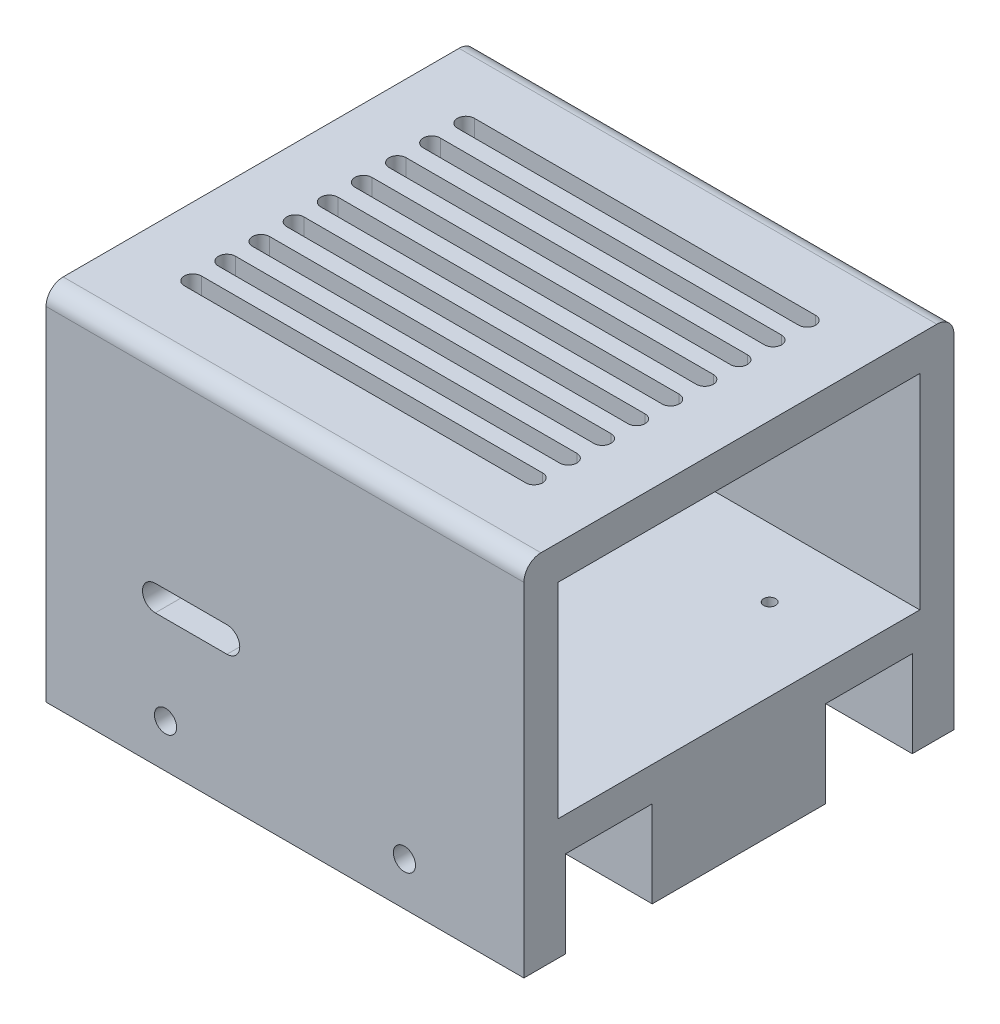
SolidWorks part; units mm, degrees
material "PETG"
ref_plane "Front Plane" through (0, 0, 0) normal (0, 0, 1) x (1, 0, 0)
ref_plane "Top Plane" through (0, 0, 0) normal (0, 1, 0) x (1, 0, 0)
ref_plane "Right Plane" through (0, 0, 0) normal (1, 0, 0) x (0, 0, -1)
sketch "Sketch1" plane through (0, 0, 0) normal (0, 1, 0) x (1, 0, 0)
  line L0 (-57.3, 38.1) -> (-70, 38.1) construction
  line L1 (-70, -25.395) -> (70, -25.395)
  line L2 (-70, -25.395) -> (-70, 25.395)
  line L3 (-70, 25.395) -> (70, 25.395)
  line L4 (70, -25.395) -> (70, 25.395)
  line L5 (-70, 52.5) -> (70, 52.5)
  line L6 (-70, 52.5) -> (-70, -52.5)
  line L7 (-70, -52.5) -> (70, -52.5)
  line L8 (70, 52.5) -> (70, -52.5)
  line L11 (57.3, 38.1) -> (70, 38.1) construction
  circle A0 centre (-57.3, 38.1) radius 3.25
  circle A1 centre (57.3, 38.1) radius 3.25
  circle A2 centre (-57.3, -38.1) radius 3.25
  circle A3 centre (57.3, -38.1) radius 3.25
  point P4 (-70, 0)
  point P5 (0, 25.395)
  dimension "D4" = 6.5
  dimension "D1" = 50.79
  dimension "D2" = 140
  dimension "D3" = 105
  dimension "D5" = 38.1
  dimension "D6" = 12.7
  dimension "D7" = 38.1
extrude "Boss-Extrude1" add sketch "Sketch1" along normal blind 10 contours L1 L4 L3 L2 | L8 L1 L6 L7 | L8 L5 L6 L3 | A1 | A0 | A2 | A3 region at (0, 0, 0) region at (0, 0, 38.9626) region at (0, 0, -38.9626) region at (-57.3, 0, -38.1) region at (57.3, 0, -38.1) region at (-57.3, 0, 38.1) region at (57.3, 0, 38.1)
extrude "Boss-Extrude2" add sketch "Sketch1<3>" against normal blind 25.4 contours L1 L4 L3 L2 region at (0, 0, 0)
sketch "Sketch1<3>" plane through (0, 0, 0) normal (0, 1, 0) x (1, 0, 0) same geometry as "Sketch1"
sketch "Sketch2" plane through (0, 10, 0) normal (0, 1, 0) x (1, 0, 0)
  line L0 (-46, 33) -> (-46, -46) construction
  line L1 (-46, -46) -> (46, -46) construction
  line L2 (46, -46) -> (46, 33) construction
  line L3 (46, 33) -> (-46, 33) construction
  line L4 (-70, -52.5) -> (70, -52.5) construction
  line L6 (-70, 52.5) -> (70, 52.5) construction
  line L7 (46, 0) -> (-46, 0) construction
  circle A0 centre (-46, 33) radius 4.5
  circle A1 centre (-46, 33) radius 1.75
  circle A2 centre (46, 33) radius 4.5
  circle A3 centre (46, 33) radius 1.75
  circle A4 centre (46, -46) radius 4.5
  circle A5 centre (46, -46) radius 1.75
  circle A6 centre (-46, -46) radius 4.5
  circle A7 centre (-46, -46) radius 1.75
  point P19 (0, 0)
  dimension "D1" = 3.5
  dimension "D2" = 9
  dimension "D3" = 6.5
  dimension "D4" = 92
  dimension "D5" = 19.5
extrude "Cut-Extrude4" cut sketch "Sketch2" against normal up to next contours A1 | A3 | A5 | A7 region at (-46, 10, -33)
sketch "Sketch3" plane through (0, 0, 0) normal (0, 1, 0) x (1, 0, 0)
  circle A0 centre (-46, 33) radius 3.2
  circle A1 centre (46, 33) radius 3.2
  circle A2 centre (46, -46) radius 3.2
  circle A3 centre (-46, -46) radius 3.2
  dimension "D1" = 6.4
extrude "Cut-Extrude3" cut sketch "Sketch3" along normal offset from surface (6.5 mm away) 3.5 up to face at (-46, 10, 47.75)
sketch "Sketch5" plane through (-70, 0, 0) normal (-1, 0, 0) x (0, 0, 1)
  line L0 (52.5, 10) -> (-52.5, 10) construction
  line L1 (-53, 0) -> (-63, 0)
  line L2 (-53, 0) -> (-53, 80)
  line L3 (-53, 80) -> (-63, 80)
  line L4 (-63, 0) -> (-63, 80)
  line L6 (-52.5, 10) -> (-53, 10)
  line L7 (53, 0) -> (63, 0)
  line L8 (53, 0) -> (53, 80)
  line L9 (53, 80) -> (63, 80)
  line L10 (63, 0) -> (63, 80)
  line L11 (-52.5, 10) -> (-52.5, 0)
  line L12 (-52.5, 0) -> (-53, 0)
  line L13 (-53, 80) -> (53, 80)
  line L14 (-53, 80) -> (-53, 70)
  line L15 (-53, 70) -> (53, 70)
  line L16 (53, 80) -> (53, 70)
  line L17 (-53, 10) -> (-53, 0)
  line L18 (52.5, 10) -> (53, 10)
  line L19 (52.5, 10) -> (52.5, 0)
  line L20 (52.5, 0) -> (53, 0)
  line L21 (53, 10) -> (53, 0)
  line M9 (52.5, 0) -> (52.5, 10)
  line M11 (-52.5, 10) -> (-52.5, 0)
  dimension "D1" = 10
  dimension "D2" = 60
  dimension "D3" = 0.5
extrude "Boss-Extrude3" add sketch "Sketch5" against normal up to surface (140 mm away) contours L4 L1 L2 L3 | L12 L6 L2 M11 | L2 L15 L8 L13 | L7 L10 L9 L8 | L20 L8 L18 M9 region at (-70, 40, -58) region at (-70, 5, -52.75) region at (-70, 75, 0) region at (-70, 40, 58) region at (-70, 5, 52.75) up to face at (70, -3.85, 0)
sketch "Sketch6" plane through (0, 0, 63) normal (0, 0, 1) x (1, 0, 0)
  line L0 (-38, 17) -> (-17, 17) construction
  line L1 (-38, 20.75) -> (-17, 20.75)
  line L2 (-38, 13.25) -> (-17, 13.25)
  line L3 (-70, 0) -> (-70, 80) construction
  line L4 (70, 0) -> (-70, 0) construction
  arc A0 (-38, 20.75) -> (-38, 13.25) centre (-38, 17) ccw
  arc A1 (-17, 13.25) -> (-17, 20.75) centre (-17, 17) ccw
  point P2 (-27.5, 17)
  dimension "D1" = 32
  dimension "D2" = 21
  dimension "D3" = 7.5
  dimension "17" = 17
extrude "Cut-Extrude6" cut sketch "Sketch6" against normal up to next
sketch "Sketch7" plane through (-70, 0, 0) normal (-1, 0, 0) x (0, 0, 1)
  line L0 (-25.395, 0) -> (-63, 0) construction
  line L1 (-63, 0) -> (-50.805, 0)
  line L2 (-63, 0) -> (-63, -25.4)
  line L3 (-63, -25.4) -> (-50.805, -25.4)
  line L4 (-50.805, 0) -> (-50.805, -25.4)
  line L5 (25.395, -25.4) -> (-25.395, -25.4) construction
  line L6 (-25.395, -25.4) -> (-25.395, 0) construction
  line L8 (63, 0) -> (50.805, 0)
  line L9 (63, 0) -> (63, -25.4)
  line L10 (63, -25.4) -> (50.805, -25.4)
  line L11 (50.805, 0) -> (50.805, -25.4)
  dimension "D1" = 25.41
extrude "Boss-Extrude4" add sketch "Sketch7" against normal up to surface (140 mm away) up to face at (70, 13.65, 0)
sketch "Sketch8" plane through (0, 0, -63) normal (0, 0, -1) x (-1, 0, 0)
  line L0 (-70, -25.4) -> (70, -25.4) construction
  line L1 (-70, 80) -> (-70, -25.4) construction
  line L2 (0, 0) -> (0, 50000) construction
  circle A0 centre (-35, -12.7) radius 3.25
  circle A2 centre (35, -12.7) radius 3.25
  dimension "D1" = 6.5
  dimension "D2" = 12.7
  dimension "D3" = 35
extrude "Cut-Extrude7" cut sketch "Sketch8" against normal up to next
mirror "Mirror1" about plane through (0, 0, 0) normal (0, 0, 1) of "Cut-Extrude7"
fillet "Fillet1" radius 5 2 edges at (0, 80, 63) (0, 80, -63)
sketch "Sketch9" plane through (0, 80, 0) normal (0, 1, 0) x (1, 0, 0)
  line L0 (-50, 40) -> (50, 40) construction
  line L1 (-50, 42.5) -> (50, 42.5)
  line L2 (-50, 37.5) -> (50, 37.5)
  line L3 (-50, 30) -> (50, 30) construction
  line L4 (-50, 32.5) -> (50, 32.5)
  line L5 (-50, 27.5) -> (50, 27.5)
  line L6 (-50, 20) -> (50, 20) construction
  line L7 (-50, 22.5) -> (50, 22.5)
  line L8 (-50, 17.5) -> (50, 17.5)
  line L9 (-50, 10) -> (50, 10) construction
  line L10 (-50, 12.5) -> (50, 12.5)
  line L11 (-50, 7.5) -> (50, 7.5)
  line L12 (-50, 0) -> (50, 0) construction
  line L13 (-50, 2.5) -> (50, 2.5)
  line L14 (-50, -2.5) -> (50, -2.5)
  line L15 (-50, -10) -> (50, -10) construction
  line L16 (-50, -7.5) -> (50, -7.5)
  line L17 (-50, -12.5) -> (50, -12.5)
  line L18 (-50, -20) -> (50, -20) construction
  line L19 (-50, -17.5) -> (50, -17.5)
  line L20 (-50, -22.5) -> (50, -22.5)
  line L21 (-50, 40) -> (-50, 30) construction
  line L22 (-50, -30) -> (50, -30) construction
  line L23 (-50, -27.5) -> (50, -27.5)
  line L24 (-50, -32.5) -> (50, -32.5)
  line L25 (-50, -40) -> (50, -40) construction
  line L26 (-50, -37.5) -> (50, -37.5)
  line L27 (-50, -42.5) -> (50, -42.5)
  arc A0 (-50, 42.5) -> (-50, 37.5) centre (-50, 40) ccw
  arc A1 (50, 37.5) -> (50, 42.5) centre (50, 40) ccw
  arc A2 (-50, 32.5) -> (-50, 27.5) centre (-50, 30) ccw
  arc A3 (50, 27.5) -> (50, 32.5) centre (50, 30) ccw
  arc A4 (-50, 22.5) -> (-50, 17.5) centre (-50, 20) ccw
  arc A5 (50, 17.5) -> (50, 22.5) centre (50, 20) ccw
  arc A6 (-50, 12.5) -> (-50, 7.5) centre (-50, 10) ccw
  arc A7 (50, 7.5) -> (50, 12.5) centre (50, 10) ccw
  arc A8 (-50, 2.5) -> (-50, -2.5) centre (-50, 0) ccw
  arc A9 (50, -2.5) -> (50, 2.5) centre (50, 0) ccw
  arc A10 (-50, -7.5) -> (-50, -12.5) centre (-50, -10) ccw
  arc A11 (50, -12.5) -> (50, -7.5) centre (50, -10) ccw
  arc A12 (-50, -17.5) -> (-50, -22.5) centre (-50, -20) ccw
  arc A13 (50, -22.5) -> (50, -17.5) centre (50, -20) ccw
  arc A14 (-50, -27.5) -> (-50, -32.5) centre (-50, -30) ccw
  arc A15 (50, -32.5) -> (50, -27.5) centre (50, -30) ccw
  arc A16 (-50, -37.5) -> (-50, -42.5) centre (-50, -40) ccw
  arc A17 (50, -42.5) -> (50, -37.5) centre (50, -40) ccw
  point P2 (0, 40)
  point P10 (0, 30)
  point P19 (0, 20)
  point P26 (0, 10)
  point P33 (0, 0)
  point P40 (0, -10)
  point P47 (0, -20)
  point P54 (0, -30)
  point P61 (0, -40)
  dimension "D1" = 100
  dimension "D2" = 5
  dimension "D3" = 40
  dimension "D5" = 10
  dimension "D4" = 9
extrude "Cut-Extrude8" cut sketch "Sketch9" against normal up to next
equation "\"tol_dia_id_intfc\" = 0.0200mm ' For hole diameters - Interference fit"
equation "\"tol_dia_id_slip\"  = 0.0300mm ' For hole diameters - Slip fit"
equation "\"tol_dia_id_clear\" = 0.0500mm ' For hole diameters - Clearance fit"
equation "\"tol_dia_od_intfc\" = 0.0200mm ' For shaft diameters - Interference fit"
equation "\"tol_dia_od_slip\"  = 0.0300mm ' For shaft diameters - Slip fit"
equation "\"tol_dia_od_clear\" = 0.0500mm ' For shaft diameters - Clearance fit"
equation "\"tol_general_intfc\"= 0.0030mm ' For general parts (Horiz) - Interference fit"
equation "\"tol_general_slip\" = 0.0050mm ' For general parts (Horiz) - Slip fit"
equation "\"tol_general_clear\"= 0.0100mm ' For general parts (Horiz) - Clearance fit"
equation "\"tol_layer_intfc\"  = 0.0030mm ' For all parts (Vert) - Interference fit"
equation "\"tol_layer_slip\"   = 0.0050mm ' For all parts (Vert) - Slip fit"
equation "\"tol_layer_clear\"  = 0.0100mm ' For all parts (Vert) - Clearance fit"
equation "\"tol_corner_rad\"   = 0.100mm ' For corners that fit into other parts"
equation "\"D1@Sketch1\"=50.80mm-\"tol_general_slip\"*2"
equation "\"D1@Sketch7\"=1in+\"tol_general_slip\"*2"
